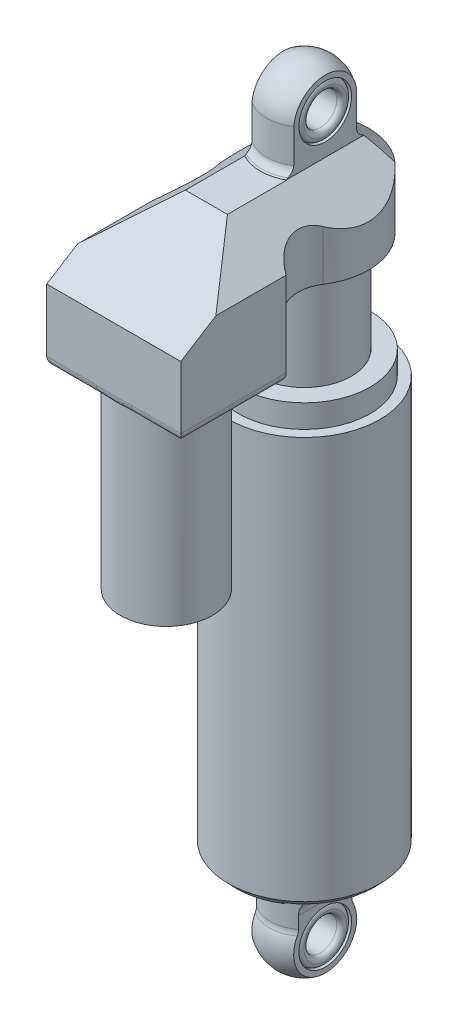
SolidWorks part; units mm, degrees
ref_plane "Front Plane" through (0, 0, 0) normal (0, 0, 1) x (1, 0, 0)
ref_plane "Top Plane" through (0, 0, 0) normal (0, 1, 0) x (1, 0, 0)
ref_plane "Right Plane" through (0, 0, 0) normal (1, 0, 0) x (0, 0, -1)
sketch "Sketch1" plane through (0, 0, 0) normal (1, 0, 0) x (0, 0, -1)
  line L0 (23, -176.33) -> (23, -55.33)
  line L10 (23, -176.33) -> (23, -177.48)
  line L11 (23, -177.48) -> (20.61, -179.97)
  line L12 (20.61, -179.97) -> (12, -182.63)
  line L13 (12, -182.63) -> (10.95, -182.63)
  line L14 (10.95, -182.63) -> (10.95, -184)
  line L15 (10.95, -184) -> (10.696, -184.2287)
  line L16 (10.696, -184.2287) -> (10.3114, -184.2287) construction
  line L17 (10.3114, -185.6983) -> (10.3114, -193.7842)
  line L19 (10.3114, -184.2287) -> (10.3114, -185.6983) construction
  line L20 (23, -55.33) -> (20, -55.33)
  line L22 (20, -55.33) -> (20, -48.33)
  line L24 (14.3114, -48.33) -> (14.3114, -17.8039)
  line L27 (19.8971, -0.2539) -> (12.9687, 5.5597)
  line L30 (14.3114, -17.8039) -> (19.8971, -17.8039)
  line L31 (0, -211.2369) -> (0, 28.87)
  line L32 (20, -48.33) -> (16.3971, -48.33)
  line L33 (11.4703, 7.8578) -> (11.4703, 18.1961)
  line L34 (19.8971, -17.8039) -> (19.8971, -0.2539)
  line L35 (14.3114, -48.33) -> (16.3971, -48.33)
  arc A0 (0, -211.2369) -> (10.6181, -195.3204) centre (0, -199.7369) ccw
  arc A2 (0, -188.2369) -> (0, -211.2369) centre (0, -199.7369) ccw construction
  arc A3 (10.3114, -194.6452) -> (0, -188.2369) centre (0, -199.7369) ccw construction
  arc A4 (10.3114, -193.7842) -> (10.6181, -195.3204) centre (14.3114, -193.7842) ccw
  arc A6 (10.696, -184.2287) -> (10.3114, -185.6983) centre (13.3114, -185.6983) ccw
  arc A7 (12.9687, 5.5597) -> (11.4703, 7.8578) centre (14.4544, 8.1659) cw
  arc A8 (11.4703, 18.1961) -> (0, 28.87) centre (0, 17.37) ccw
  point P8 (0, 0)
  point P11 (0, 0)
  point P16 (23, -176.13)
  point P26 (0, 0)
  point P36 (0, 0)
  point P37 (0, 0)
  point P38 (0, 0)
  dimension "D2" = 23
  dimension "D24" = 4
  dimension "D25" = 3
  dimension "D6" = 7
  dimension "D7" = 42
  dimension "D27" = 0.2
revolve "Revolve1" add sketch "Sketch1" angle 360 about L31
sketch "Sketch2" plane through (0, 0, 0) normal (0, 0, 1) x (1, 0, 0)
  line L0 (0, 0) -> (0, -233.0262) construction
  line L1 (6.35, -209.2179) -> (6.35, -190.13)
  line L2 (22.5, -179.23) -> (22.5, -214.63)
  line L3 (9.35, -184.9338) -> (9.35, -182.63)
  line L4 (9.35, -182.63) -> (11, -182.63)
  line L5 (11, -182.63) -> (11, -180.03)
  line L6 (11.8, -179.23) -> (22.5, -179.23)
  line L7 (22.5, -214.63) -> (6.35, -214.63)
  line L8 (6.35, -214.63) -> (6.35, -209.2179)
  line L9 (-6.35, -214.63) -> (-6.35, -209.2179)
  line L10 (-22.5, -214.63) -> (-6.35, -214.63)
  line L11 (-11.8, -179.23) -> (-22.5, -179.23)
  line L12 (-11, -182.63) -> (-11, -180.03)
  line L13 (-9.35, -182.63) -> (-11, -182.63)
  line L14 (-9.35, -184.9338) -> (-9.35, -182.63)
  line L15 (-22.5, -179.23) -> (-22.5, -214.63)
  line L16 (-6.35, -209.2179) -> (-6.35, -190.13)
  arc A0 (-6.35, -209.2179) -> (6.35, -209.2179) centre (0, -199.63) ccw construction
  arc A1 (11, -180.03) -> (11.8, -179.23) centre (11.8, -180.03) cw
  arc A2 (6.35, -190.13) -> (9.35, -184.9338) centre (12.35, -190.13) cw
  arc A3 (-6.35, -190.13) -> (-9.35, -184.9338) centre (-12.35, -190.13) ccw
  arc A4 (-11, -180.03) -> (-11.8, -179.23) centre (-11.8, -180.03) ccw
  dimension "D2" = 23
  dimension "D4" = 6
  dimension "D12" = 0.8
  dimension "D1" = 199.63
  dimension "D3" = 12.7
  dimension "D5" = 9.5
  dimension "D6" = 18.7
  dimension "D7" = 17
  dimension "D8" = 11
  dimension "D9" = 20.4
  dimension "D10" = 45
  dimension "D11" = 15
extrude "Cut-Extrude2" cut sketch "Sketch2" against normal through all both and the other way through all
sketch "Sketch4" plane through (0, 0, 0) normal (1, 0, 0) x (0, 0, -1)
  line L0 (-25.8947, -34.4477) -> (-57.9666, -34.4477)
  line L1 (0, -211.2369) -> (0, 28.87) construction
  line L2 (0, 5.21) -> (-29.7732, 5.21)
  line L3 (0, 5.21) -> (0, -17.8039)
  line L4 (-14.3114, -17.8039) -> (14.3114, -17.8039) construction
  line L5 (0, -17.8039) -> (-25.0097, -17.8039)
  line L8 (-57.8947, -12.4477) -> (-29.7732, 5.21)
  line L9 (-57.8947, -12.4477) -> (-57.8947, -34.4477)
  line L12 (-25.8947, -34.4477) -> (-25.0097, -17.8039)
  line L13 (-25.8947, -34.4477) -> (-25.8947, -90.4477)
  line L14 (-57.9666, -34.4477) -> (-57.9666, -90.4477)
  line L15 (-57.9666, -90.4477) -> (-25.8947, -90.4477)
  dimension "D1" = 56
  dimension "D2" = 22
  dimension "D3" = 28.1215
  dimension "D4" = 29.7732
  dimension "D5" = 23.0139
  dimension "D6" = 25.0097
  dimension "D7" = 16.6438
  dimension "D8" = 32.0718
extrude "Boss-Extrude2" add sketch "Sketch4" along normal through all and the other way through all contours L0 L12 L5 L3 L2 L8 L9
sketch "Sketch5" plane through (0, 0, 0) normal (0, 1, 0) x (1, 0, 0)
  line L0 (38.7311, 0) -> (-38.7311, 0) construction
  line L1 (0, 0) -> (0, 19.5) construction
  line L2 (-25.2, -27.0612) -> (25.2, -27.0612) construction
  line L3 (-25.2, -27.0612) -> (-25.2, 28)
  line L4 (-25.2, 28) -> (25.2, 28)
  line L5 (25.2, -27.0612) -> (25.2, 28)
  arc A0 (16.3256, -10.6642) -> (-16.3256, -10.6642) centre (0, 0) ccw
  arc A1 (-25.2, -27.0612) -> (-16.3256, -10.6642) centre (-25.2, -16.4612) ccw
  arc A2 (25.2, -27.0612) -> (16.3256, -10.6642) centre (25.2, -16.4612) cw
  point P9 (0, -27.0612)
  point P13 (0, 28)
  dimension "D1" = 39
  dimension "D2" = 21.2
  dimension "D3" = 28
extrude "Cut-Extrude5" cut sketch "Sketch5" against normal blind 35 and the other way blind 39
sketch "Sketch3" plane through (0, 0, 0) normal (0, 0, 1) x (1, 0, 0)
  line L0 (26.9211, 30.7689) -> (26.9211, -10.908)
  line L3 (-6.35, 30.7694) -> (-6.35, 5.21)
  line L4 (6.3502, 30.7689) -> (6.3502, 5.2645)
  line L5 (-6.35, 30.7694) -> (-25.4049, 30.7694)
  line L6 (6.3502, 30.7689) -> (26.9211, 30.7689)
  line L7 (-25.4049, 30.7694) -> (-25.4049, -10.7789)
  line L9 (-25.4049, -10.7789) -> (-6.35, 5.21)
  line L10 (6.3502, 5.2645) -> (26.9211, -10.908)
extrude "Cut-Extrude3" cut sketch "Sketch3" against normal through all both and the other way through all
sketch "Sketch6" plane through (0, -90.4477, 0) normal (0, -1, 0) x (1, 0, 0)
  line L6 (-23, 57.9666) -> (-23, 25.8947)
  line L7 (-23, 25.8947) -> (23, 25.8947)
  line L8 (23, 25.8947) -> (23, 57.9666)
  line L9 (23, 57.9666) -> (-23, 57.9666)
  circle A0 centre (0, 41.9307) radius 14
  dimension "D1" = 28
extrude "Cut-Extrude6" cut sketch "Sketch6" against normal blind 56
sketch "Sketch7" plane through (0, 0, 0) normal (0, 0, 1) x (1, 0, 0)
  line L0 (-33.5494, -34.4477) -> (-33.5494, -37.3052)
  line L1 (23, -34.4477) -> (-23, -34.4477) construction
  line L2 (20.366, -34.4477) -> (20.366, -37.3052)
  line L3 (-20.366, -34.4477) -> (-20.366, 6.4507)
  line L4 (-33.5494, 6.4507) -> (-33.5494, -34.4477)
  line L7 (29.9265, -34.4477) -> (29.9265, 6.4507)
  line L8 (29.9265, 6.4507) -> (20.366, 6.4507)
  line L9 (20.366, 6.4507) -> (20.366, -34.4477)
  line L10 (-20.366, 6.4507) -> (-33.5494, 6.4507)
  line L11 (-33.5494, -37.3052) -> (-20.366, -37.3052)
  line L12 (-20.366, -37.3052) -> (-20.366, -34.4477)
  line L13 (20.366, -37.3052) -> (29.9265, -37.3052)
  line L14 (29.9265, -37.3052) -> (29.9265, -34.4477)
extrude "Cut-Extrude7" cut sketch "Sketch7" against normal through all and the other way through all contours L10 L4 L0 L11 L12 L3 | L14 L7 L8 L9 L2 L13
fillet "Fillet5" radius 3 4 edges at (0, -34.4477, 57.8947) (-20.366, -34.4477, 41.8947) (0, -34.4477, 25.8947) (20.366, -34.4477, 41.8947)
sketch "Sketch10" plane through (0, 0, 0) normal (1, 0, 0) x (0, 0, -1)
  circle A0 centre (0, 17.37) radius 8
extrude "Cut-Extrude12" cut sketch "Sketch10" against normal through all both and the other way through all
sketch "Sketch21" plane through (0, 0, 0) normal (1, 0, 0) x (0, 0, -1)
  circle A0 centre (0, 17.37) radius 8
  dimension "D1" = 16
extrude "Boss-Extrude8" add sketch "Sketch21" along normal mid plane 8
sketch "Sketch22" plane through (4, 0, 0) normal (1, 0, 0) x (0, 0, -1)
  circle A0 centre (0, 17.37) radius 7.95
  circle A1 centre (0, 17.37) radius 4.99
extrude "Boss-Extrude9" add sketch "Sketch22" along normal blind 2.35 contours A0 | A1
fillet "Fillet8" radius 1.47 2 edges at (6.35, 17.37, -7.95) (6.35, 17.37, -4.99)
mirror "Mirror4" about plane through (0, 0, 0) normal (1, 0, 0) of "Boss-Extrude9", "Fillet8"
sketch "Sketch23" plane through (4, 0, 0) normal (1, 0, 0) x (0, 0, -1)
  circle A0 centre (0, 17.37) radius 4.99
extrude "Cut-Extrude13" cut sketch "Sketch23" against normal through all both and the other way through all contours A0
sketch "Sketch17" plane through (0, 0, 0) normal (1, 0, 0) x (0, 0, -1)
  circle A0 centre (0, -199.7369) radius 8
extrude "Cut-Extrude10" cut sketch "Sketch17" against normal through all both and the other way through all contours A0
sketch "Sketch18" plane through (0, 0, 0) normal (1, 0, 0) x (0, 0, -1)
  circle A0 centre (0, -199.7369) radius 8
extrude "Boss-Extrude5" add sketch "Sketch18" along normal mid plane 8 contours A0
sketch "Sketch19" plane through (4, 0, 0) normal (1, 0, 0) x (0, 0, -1)
  circle A0 centre (0, -199.7369) radius 7.95
  circle A1 centre (0, -199.7369) radius 4.99
extrude "Boss-Extrude6" add sketch "Sketch19" along normal blind 2.35
fillet "Fillet7" radius 1.47 2 edges at (6.35, -199.7369, -7.95) (6.35, -199.7369, -4.99)
mirror "Mirror3" about plane through (0, 0, 0) normal (1, 0, 0) of "Boss-Extrude6", "Fillet7"
sketch "Sketch24" plane through (4, 0, 0) normal (1, 0, 0) x (0, 0, -1)
  circle A0 centre (0, -199.7369) radius 4.99
extrude "Cut-Extrude14" cut sketch "Sketch24" against normal through all both and the other way through all
